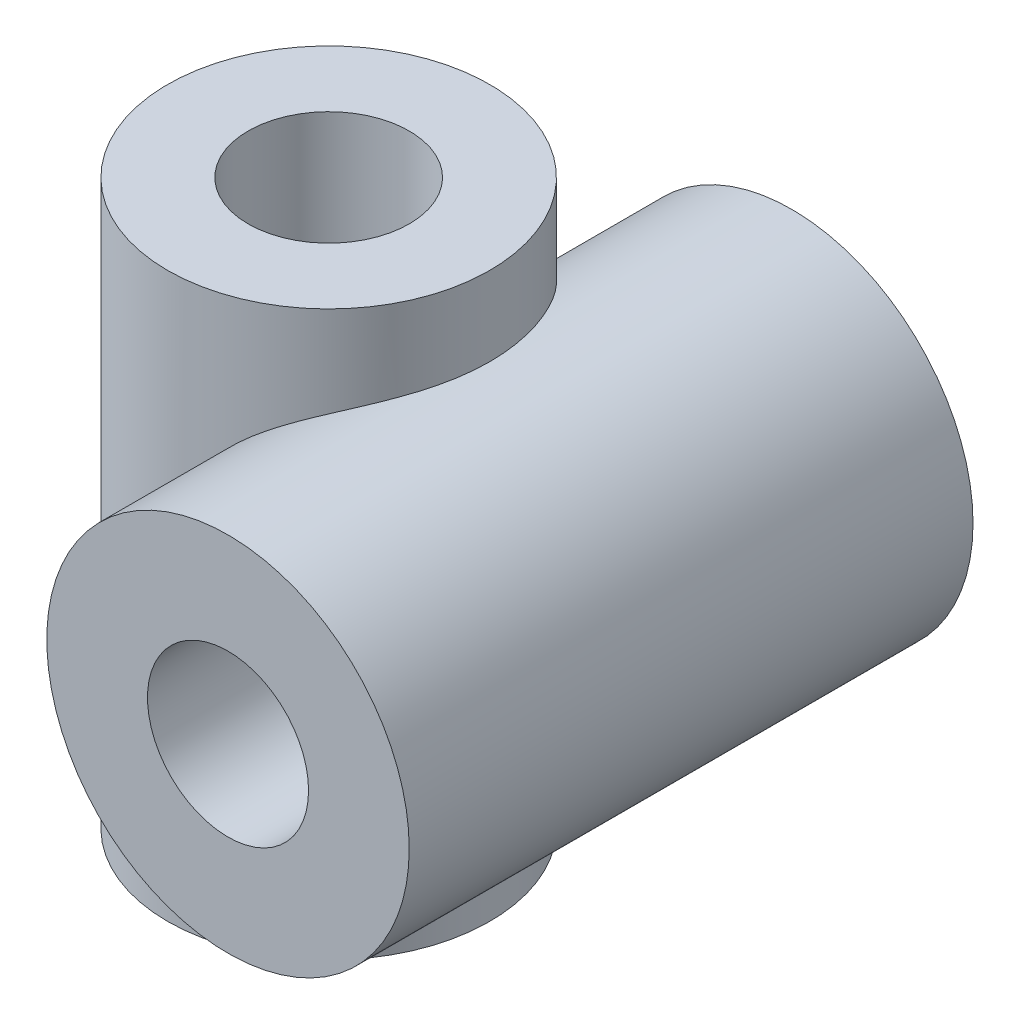
SolidWorks part; units mm, degrees
material "Gray Cast Iron"
ref_plane "Front Plane" through (0, 0, 0) normal (0, 0, 1) x (1, 0, 0)
ref_plane "Top Plane" through (0, 0, 0) normal (0, 1, 0) x (1, 0, 0)
ref_plane "Right Plane" through (0, 0, 0) normal (1, 0, 0) x (0, 0, -1)
sketch "Sketch1" plane through (0, 0, 0) normal (0, 1, 0) x (1, 0, 0)
  circle A0 centre (0, 0) radius 16
  circle A1 centre (0, 0) radius 8
extrude "Boss-Extrude1" add sketch "Sketch1" along normal blind 56
sketch "Sketch2" plane through (0, 0, 0) normal (0, 0, 1) x (1, 0, 0)
  line L0 (0, 56) -> (0, 0) construction
  circle A0 centre (18, 30.2581) radius 8
  circle A1 centre (18, 30.2581) radius 18
  dimension "D1" = 36
  dimension "D2" = 16
  dimension "D3" = 18
extrude "Boss-Extrude2" add sketch "Sketch2" along normal blind 28 and the other way blind 28
sketch "Sketch3" plane through (0, 56, 0) normal (0, 1, 0) x (1, 0, 0)
  circle A0 centre (0, 0) radius 8
extrude "Cut-Extrude1" cut sketch "Sketch3" against normal through all
sketch "Sketch4" plane through (0, 0, 28) normal (0, 0, 1) x (1, 0, 0)
  circle A0 centre (18, 30.2581) radius 8
extrude "Cut-Extrude2" cut sketch "Sketch4" against normal through all
